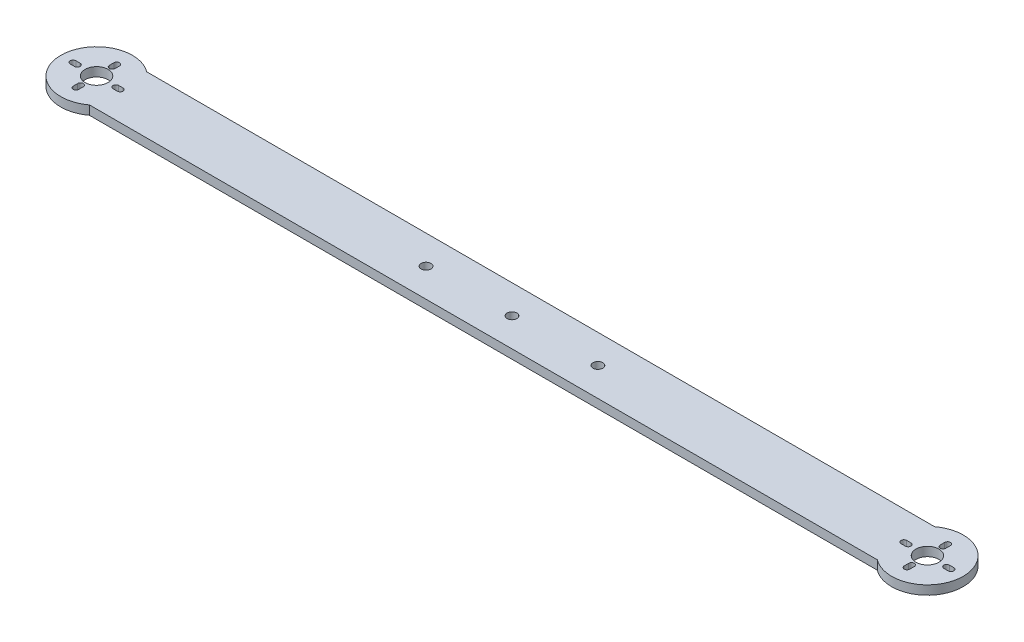
SolidWorks part; units mm, degrees
ref_plane "Front Plane" through (0, 0, 0) normal (0, 0, 1) x (1, 0, 0)
ref_plane "Top Plane" through (0, 0, 0) normal (0, 1, 0) x (1, 0, 0)
ref_plane "Right Plane" through (0, 0, 0) normal (1, 0, 0) x (0, 0, -1)
sketch "Sketch1" plane through (0, 0, 0) normal (0, 1, 0) x (1, 0, 0)
  line L0 (0, 12.7) -> (0, -12.7) construction
  line L1 (-174.625, 12.7) -> (174.625, 12.7)
  line L3 (-174.625, -12.7) -> (174.625, -12.7)
  arc A0 (-174.625, 12.7) -> (-174.625, -12.7) centre (-184.15, 0) ccw
  arc A1 (174.625, -12.7) -> (174.625, 12.7) centre (184.15, 0) ccw
  point P8 (0, 12.7)
  point P12 (0, 0)
  dimension "D3" = 31.75
  dimension "D4" = 31.75
extrude "Boss-Extrude1" add sketch "Sketch1" along normal blind 4
sketch "Sketch2" plane through (0, 4, 0) normal (0, 1, 0) x (1, 0, 0)
  line L0 (173.6914, 0) -> (175.6086, 0) construction
  line L1 (173.6914, 1.25) -> (175.6086, 1.25)
  line L2 (173.6914, -1.25) -> (175.6086, -1.25)
  line L3 (184.15, 0) -> (184.15, 3.2374) construction
  line L4 (194.6086, 0) -> (192.6914, 0) construction
  line L5 (194.6086, 1.25) -> (192.6914, 1.25)
  line L6 (194.6086, -1.25) -> (192.6914, -1.25)
  line L7 (184.15, 8.9209) -> (184.15, 6.921) construction
  line L8 (185.4, 8.9209) -> (185.4, 6.921)
  line L9 (182.9, 8.9209) -> (182.9, 6.921)
  line L10 (184.1914, -9.079) -> (184.1914, -7.079) construction
  line L11 (185.4414, -9.079) -> (185.4414, -7.079)
  line L12 (182.9414, -9.079) -> (182.9414, -7.079)
  line L13 (0, 0) -> (184.15, 0) construction
  line L14 (0, 0) -> (0, 12.7) construction
  line L15 (174.625, 12.7) -> (-174.625, 12.7) construction
  line L16 (-184.15, 0) -> (-184.15, 3.2374) construction
  line L17 (-184.1914, -9.079) -> (-184.1914, -7.079) construction
  line L18 (-185.4414, -9.079) -> (-185.4414, -7.079)
  line L19 (-182.9414, -9.079) -> (-182.9414, -7.079)
  line L20 (-184.15, 8.9209) -> (-184.15, 6.921) construction
  line L21 (-185.4, 8.9209) -> (-185.4, 6.921)
  line L22 (-182.9, 8.9209) -> (-182.9, 6.921)
  line L23 (-194.6086, 0) -> (-192.6914, 0) construction
  line L24 (-194.6086, 1.25) -> (-192.6914, 1.25)
  line L25 (-194.6086, -1.25) -> (-192.6914, -1.25)
  line L26 (-173.6914, 0) -> (-175.6086, 0) construction
  line L27 (-173.6914, 1.25) -> (-175.6086, 1.25)
  line L28 (-173.6914, -1.25) -> (-175.6086, -1.25)
  circle A0 centre (184.15, 0) radius 5.08
  arc A1 (173.6914, 1.25) -> (173.6914, -1.25) centre (173.6914, 0) ccw
  arc A2 (175.6086, -1.25) -> (175.6086, 1.25) centre (175.6086, 0) ccw
  arc A3 (194.6086, 1.25) -> (194.6086, -1.25) centre (194.6086, 0) cw
  arc A4 (192.6914, -1.25) -> (192.6914, 1.25) centre (192.6914, 0) cw
  arc A5 (185.4, 8.9209) -> (182.9, 8.9209) centre (184.15, 8.9209) ccw
  arc A6 (182.9, 6.921) -> (185.4, 6.921) centre (184.15, 6.921) ccw
  arc A7 (185.4414, -9.079) -> (182.9414, -9.079) centre (184.1914, -9.079) cw
  arc A8 (182.9414, -7.079) -> (185.4414, -7.079) centre (184.1914, -7.079) cw
  circle A9 centre (-184.15, 0) radius 5.08
  arc A10 (-185.4414, -9.079) -> (-182.9414, -9.079) centre (-184.1914, -9.079) ccw
  arc A11 (-182.9414, -7.079) -> (-185.4414, -7.079) centre (-184.1914, -7.079) ccw
  arc A12 (-185.4, 8.9209) -> (-182.9, 8.9209) centre (-184.15, 8.9209) cw
  arc A13 (-182.9, 6.921) -> (-185.4, 6.921) centre (-184.15, 6.921) cw
  arc A14 (-194.6086, 1.25) -> (-194.6086, -1.25) centre (-194.6086, 0) ccw
  arc A15 (-192.6914, -1.25) -> (-192.6914, 1.25) centre (-192.6914, 0) ccw
  arc A16 (-173.6914, 1.25) -> (-173.6914, -1.25) centre (-173.6914, 0) cw
  arc A17 (-175.6086, -1.25) -> (-175.6086, 1.25) centre (-175.6086, 0) cw
  point P4 (174.65, 0)
  point P12 (193.65, 0)
  point P19 (184.15, 7.921)
  point P26 (184.1914, -8.079)
  point P41 (-184.1914, -8.079)
  point P48 (-184.15, 7.921)
  point P55 (-193.65, 0)
  point P62 (-174.65, 0)
  point P67 (0, 0)
  point P68 (0, 0)
  dimension "D4" = 10.16
  dimension "D1" = 16
  dimension "D2" = 19
  dimension "D3" = 184.15
  dimension "D5" = 1.9999
extrude "Cut-Extrude1" cut sketch "Sketch2" against normal through all
sketch "Sketch3" plane through (0, 4, 0) normal (0, 1, 0) x (1, 0, 0)
  circle A0 centre (0, 0) radius 2.159
  circle A1 centre (38.1, 0) radius 2.159
  circle A2 centre (-38.1, 0) radius 2.159
  dimension "D1" = 38.1
  dimension "D3" = 4.318
  dimension "D4" = 4.318
  dimension "D5" = 4.318
  dimension "D2" = 38.1
extrude "Cut-Extrude2" cut sketch "Sketch3" against normal through all
